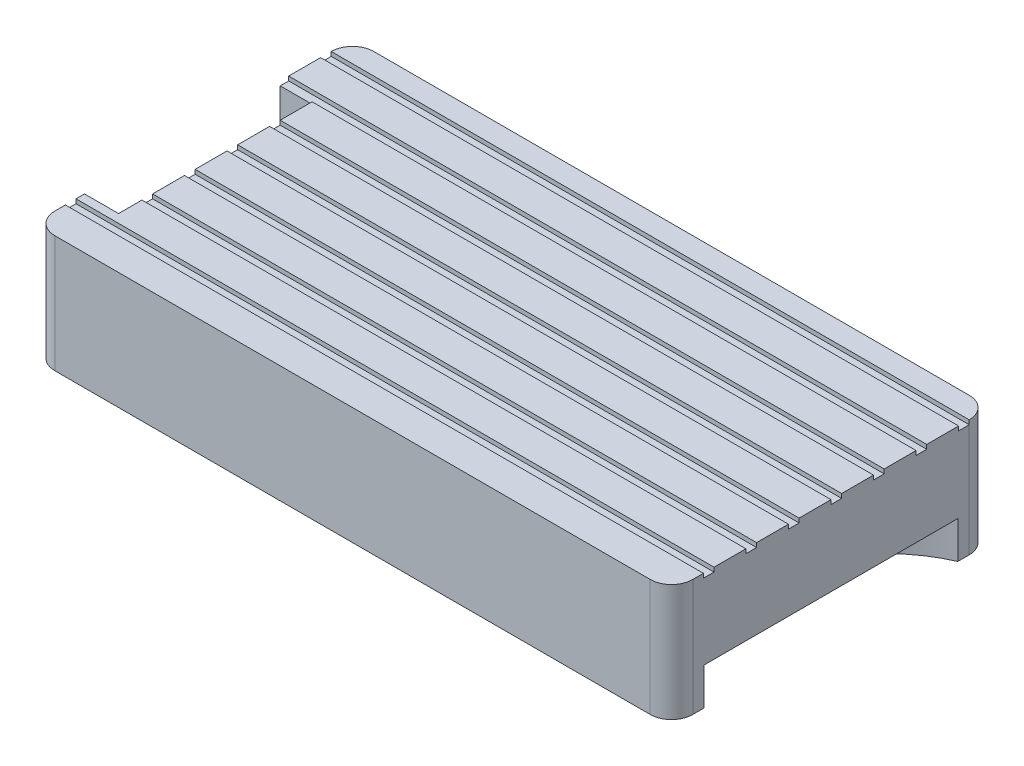
SolidWorks part; units mm, degrees
material "Copper"
ref_plane "Front Plane" through (0, 0, 0) normal (0, 0, 1) x (1, 0, 0)
ref_plane "Top Plane" through (0, 0, 0) normal (0, 1, 0) x (1, 0, 0)
ref_plane "Right Plane" through (0, 0, 0) normal (1, 0, 0) x (0, 0, -1)
sketch "Sketch1" plane through (0, 0, 0) normal (0, 1, 0) x (1, 0, 0)
  line L0 (-15, 0) -> (0, 0) construction
  line L1 (-15, -7.5) -> (15, -7.5)
  line L2 (-15, -7.5) -> (-15, 7.5)
  line L3 (-15, 7.5) -> (15, 7.5)
  line L4 (15, -7.5) -> (15, 7.5)
  line L5 (0, 0) -> (0, -7.5) construction
  dimension "D1" = 15
  dimension "D2" = 30
extrude "Boss-Extrude1" add sketch "Sketch1" along normal blind 5.5
sketch "Sketch2" plane through (0, 0, 0) normal (1, 0, 0) x (0, 0, -1)
  line L0 (-7.5, 5.5) -> (7.5, 5.5) construction
  line L1 (-6, 5.5) -> (-5.5, 5.5)
  line L2 (-6, 5.5) -> (-6, 5.3)
  line L3 (-6, 5.3) -> (-5.5, 5.3)
  line L4 (-5.5, 5.5) -> (-5.5, 5.3)
  line L5 (-7.5, 5.5) -> (-7.5, 0) construction
  line L6 (-3.5, 5.5) -> (-3.5, 5.3)
  line L7 (-4, 5.5) -> (-3.5, 5.5)
  line L8 (-4, 5.5) -> (-4, 5.3)
  line L9 (-4, 5.3) -> (-3.5, 5.3)
  line L10 (-1.5, 5.5) -> (-1.5, 5.3)
  line L11 (-2, 5.5) -> (-1.5, 5.5)
  line L12 (-2, 5.5) -> (-2, 5.3)
  line L13 (-2, 5.3) -> (-1.5, 5.3)
  line L14 (0.5, 5.5) -> (0.5, 5.3)
  line L15 (0, 5.5) -> (0.5, 5.5)
  line L16 (0, 5.5) -> (0, 5.3)
  line L17 (0, 5.3) -> (0.5, 5.3)
  line L18 (2.5, 5.5) -> (2.5, 5.3)
  line L19 (2, 5.5) -> (2.5, 5.5)
  line L20 (2, 5.5) -> (2, 5.3)
  line L21 (2, 5.3) -> (2.5, 5.3)
  line L22 (4.5, 5.5) -> (4.5, 5.3)
  line L23 (4, 5.5) -> (4.5, 5.5)
  line L24 (4, 5.5) -> (4, 5.3)
  line L25 (4, 5.3) -> (4.5, 5.3)
  line L26 (6.5, 5.5) -> (6.5, 5.3)
  line L27 (6, 5.5) -> (6.5, 5.5)
  line L28 (6, 5.5) -> (6, 5.3)
  line L29 (6, 5.3) -> (6.5, 5.3)
  dimension "D1" = 0.2
  dimension "D2" = 0.5
  dimension "D3" = 1.5
  dimension "D5" = 1.5
  dimension "D4" = 7
extrude "Cut-Extrude2" cut sketch "Sketch2" against normal through all both and the other way through all
ref_plane "Plane1" through (0, 0, 4) normal (0, 0, 1) x (1, 0, 0)
sketch "Sketch8" plane through (0, 0, 4) normal (0, 0, 1) x (1, 0, 0)
  line L0 (10.25, 0) -> (10.25, 3)
  line L1 (-15, 0) -> (15, 0) construction
  line L2 (10.25, 3) -> (9, 3.7217)
  line L3 (9, 3.7217) -> (9, 0)
  line L4 (9, 0) -> (10.25, 0)
  line L5 (0, 0) -> (0, 7.2512) construction
  line L6 (9, 0) -> (9, 5.5) construction
  line L7 (-15, 5.5) -> (15, 5.5) construction
  dimension "D1" = 18
  dimension "D2" = 2.5
  dimension "D3" = 3
  dimension "D4" = 60
revolve "Cut-Revolve1" cut sketch "Sketch8" angle 360 about L6
mirror "Mirror1" about plane through (0, 0, 0) normal (0, 0, 1) of "Cut-Revolve1"
mirror "Mirror2" about plane through (0, 0, 0) normal (1, 0, 0) of "Mirror1"
sketch "Sketch5" plane through (-15, 0, 0) normal (1, 0, 0) x (0, 0, -1)
  line L0 (-7.5, 0) -> (7.5, 0) construction
  line L1 (4.1, 0) -> (-5.1, 0)
  line L2 (4.1, 0) -> (4.1, 5.5)
  line L3 (4.1, 5.5) -> (-5.1, 5.5)
  line L4 (-5.1, 0) -> (-5.1, 5.5)
  line L5 (-3.5, 5.5) -> (-2, 5.5) construction
  line L6 (7.5, 0) -> (-7.5, 0) construction
  line L7 (-0.5, 0) -> (-0.5, 5.5) construction
  dimension "D1" = 9.2
  dimension "D2" = 0.5
extrude "Cut-Extrude4" cut sketch "Sketch5" along normal blind 1.6
sketch "Sketch9" plane through (0, 0, 0) normal (0, 0, 1) x (1, 0, 0)
  line L0 (-15, 2.5) -> (-7.6783, 2.5)
  line L1 (-15, 5.5) -> (-15, 0) construction
  line L2 (-7.6783, 2.5) -> (-8.4, 3.75)
  line L3 (-8.4, 3.75) -> (-15, 3.75)
  line L4 (-15, 3.75) -> (-15, 2.5)
  line L5 (-15, 2.5) -> (-16.9854, 2.5) construction
  line L6 (15, 0) -> (-15, 0) construction
  dimension "D1" = 2.5
  dimension "D2" = 6.6
  dimension "D3" = 60
  dimension "D4" = 2.5
revolve "Cut-Revolve2" cut sketch "Sketch9" angle 360 about L5
sketch "Sketch7" plane through (0, 0, 0) normal (0, -1, 0) x (1, 0, 0)
  line L0 (17.59, 0) -> (0, 0) construction
  circle A0 centre (17.59, 0) radius 6.5
  dimension "D1" = 13
  dimension "D2" = 17.59
extrude "Cut-Extrude6" cut sketch "Sketch7" against normal blind 1.75
fillet "Fillet1" radius 1 4 edges at (-15, 2.75, 7.5) (-15, 2.75, -7.5) (15, 2.75, -7.5) (15, 2.75, 7.5)
